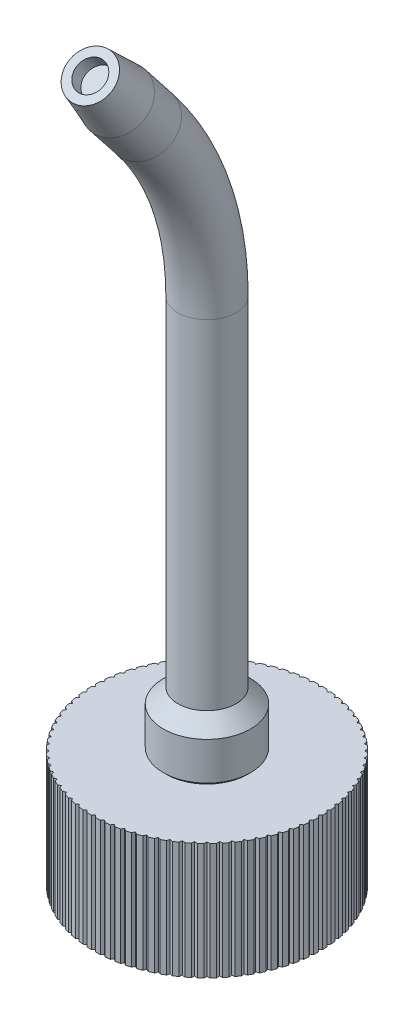
SolidWorks part; units mm, degrees
ref_plane "前视基准面" through (0, 0, 0) normal (0, 0, 1) x (1, 0, 0)
ref_plane "上视基准面" through (0, 0, 0) normal (0, 1, 0) x (1, 0, 0)
ref_plane "右视基准面" through (0, 0, 0) normal (1, 0, 0) x (0, 0, -1)
sketch "草图4" plane through (0, 0, 0) normal (0, 1, 0) x (1, 0, 0)
  circle A0 centre (0, 0) radius 10
  dimension "D1" = 20
sketch "草图6" plane through (0, 0, 0) normal (1, 0, 0) x (0, 0, -1)
  line L0 (0, 0) -> (0, 115.2978)
  line L1 (-21.4962, 177.2425) -> (-40.0796, 200.7937)
  arc A0 (-21.4962, 177.2425) -> (0, 115.2978) centre (-100, 115.2978) cw
  point P6 (0, 150)
  dimension "D2" = 100
  dimension "D3" = 30
  dimension "D1" = 150
sweep "扫描7" add profiles "草图4" path "草图6"
sketch "草图7" plane through (0, 0, 0) normal (0, -1, 0) x (1, 0, 0)
  circle A0 centre (0, 0) radius 15
  dimension "D1" = 30
extrude "凸台-拉伸2" add sketch "草图7" along normal blind 20
chamfer "倒角1" distance 6 angle 45 1 edges at (0, 0, -15)
chamfer "倒角2" distance 1 angle 45 1 edges at (0, -20, -15)
sketch "草图8" plane through (0, -20, 0) normal (0, -1, 0) x (1, 0, 0)
  circle A0 centre (0, 0) radius 39
  dimension "D1" = 78
extrude "凸台-拉伸3" add sketch "草图8" along normal blind 40
sketch "草图9" plane through (0, -60, 0) normal (0, -1, 0) x (1, 0, 0)
  line L0 (0, 0) -> (-50000, 0) construction
  line L1 (0, 42.1417) -> (0, -30.1961) construction
  line L2 (-0.7071, 38.9936) -> (0, 38.2865)
  line L3 (0, 38.2865) -> (0.7071, 38.9936)
  circle A0 centre (0, 0) radius 39 construction
  arc A1 (-39, 0) -> (39, 0) centre (0, 0) ccw
  arc A2 (0.7071, 38.9936) -> (-0.7071, 38.9936) centre (0, 0) ccw
  dimension "D1" = 1
  dimension "D2" = 1
extrude "切除-拉伸1" cut sketch "草图9" against normal up to next contours L2 L3 A2
pattern_circular "阵列(圆周)1" count 80 over 360 about axis through (0, -60, 0) along (0, -1, 0) of "切除-拉伸1"
sketch "草图10" plane through (0, 143.2365, 113.023) normal (0, 0.785, 0.6194) x (1, 0, 0)
  circle A0 centre (0, 92.9171) radius 5
  dimension "D1" = 10
extrude "切除-拉伸2" cut sketch "草图10" against normal blind 5
chamfer "倒角3" distance 15 angle 8 1 edges at (0, 194.5992, 47.93) first distance on face at (0, 171.0481, 29.3465)
sketch "草图11" plane through (0, -60, 0) normal (0, -1, 0) x (1, 0, 0)
  circle A0 centre (0, 0) radius 30
  dimension "D1" = 60
extrude "切除-拉伸3" cut sketch "草图11" against normal blind 20
sketch "草图12" plane through (0, -60, 0) normal (0, -1, 0) x (1, 0, 0)
  line L0 (0, -6.445) -> (0, 86.1696) construction
  line L1 (-46.7208, 0) -> (65.1377, 0) construction
  circle A0 centre (34, 0) radius 2.5
  point P7 (0, 0)
  dimension "D1" = 5
  dimension "D2" = 34
extrude "切除-拉伸4" cut sketch "草图12" against normal blind 10
pattern_circular "阵列(圆周)2" count 4 over 360 about axis through (0, -60, 0) along (0, -1, 0) of "切除-拉伸4"
